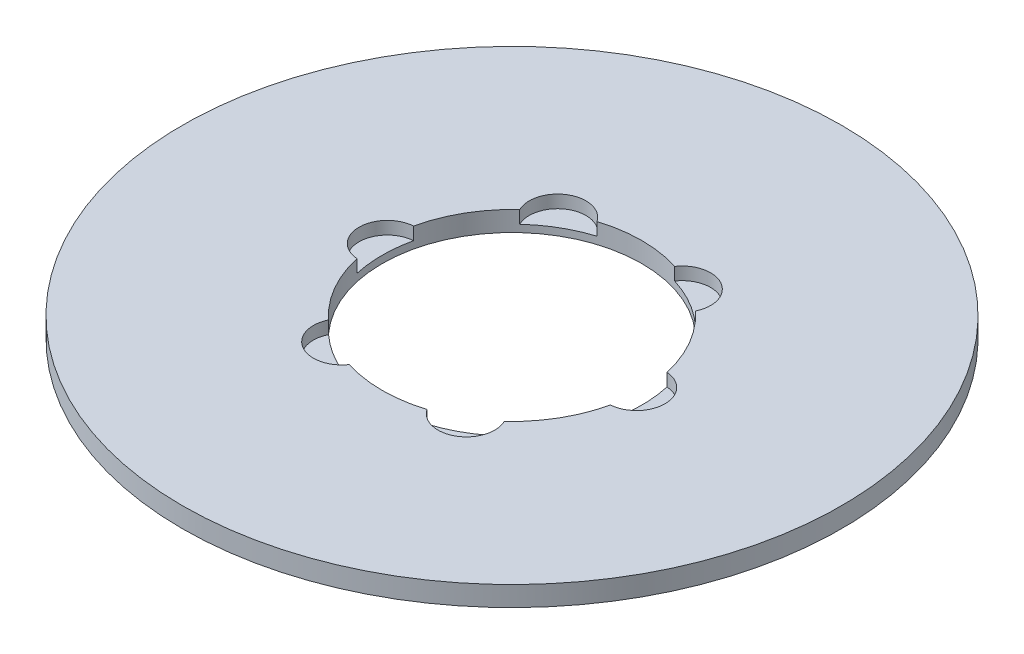
SolidWorks part; units mm, degrees
ref_plane "Front Plane" through (0, 0, 0) normal (0, 0, 1) x (1, 0, 0)
ref_plane "Top Plane" through (0, 0, 0) normal (0, 1, 0) x (1, 0, 0)
ref_plane "Right Plane" through (0, 0, 0) normal (1, 0, 0) x (0, 0, -1)
sketch "Sketch1" plane through (0, 0, 0) normal (0, 1, 0) x (1, 0, 0)
  circle A0 centre (0, 0) radius 82.5
  dimension "FLANGE_OD" = 165
extrude "Boss-Extrude1" add sketch "Sketch1" along normal blind 5
sketch "Sketch2" plane through (0, 0, 0) normal (0, 1, 0) x (1, 0, 0)
  circle A0 centre (0, 0) radius 32.5
  dimension "BORE_D" = 65
extrude "Cut-Extrude1" cut sketch "Sketch2" along normal through all
sketch "Sketch3" plane through (0, 5, 0) normal (0, 1, 0) x (1, 0, 0)
  circle A0 centre (0, 0) radius 31.1892 construction
  circle A1 centre (-31.1892, 0) radius 7.1076
  dimension "BOLT_D" = 14.2151
  dimension "BOLT_PCD" = 62.3784
extrude "Cut-Extrude2" cut sketch "Sketch3" against normal blind 3.1812
pattern_circular "CirPattern1" count 6 over 360 about axis through (0, 0, 0) along (0, 1, 0) of "Cut-Extrude2"
